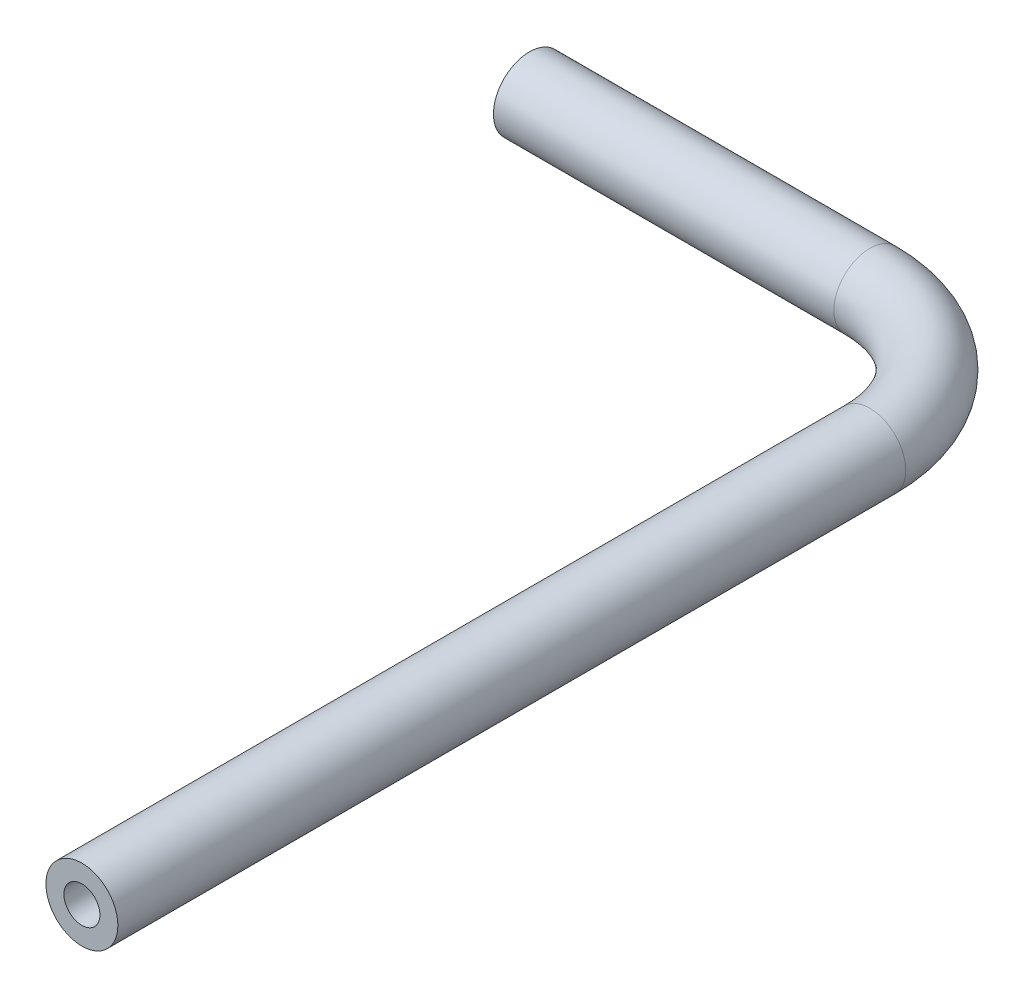
SolidWorks part; units mm, degrees
ref_plane "Front Plane" through (0, 0, 0) normal (0, 0, 1) x (1, 0, 0)
ref_plane "Top Plane" through (0, 0, 0) normal (0, 1, 0) x (1, 0, 0)
ref_plane "Right Plane" through (0, 0, 0) normal (1, 0, 0) x (0, 0, -1)
sketch "Sketch10" plane through (0, 0, 0) normal (0, 1, 0) x (1, 0, 0)
  line L0 (60.8594, -106.5557) -> (60.8594, -6.4079)
  line L1 (43.2668, 11.1847) -> (0, 11.1847)
  line L2 (0, -55) -> (0, 55) construction
  arc A0 (60.8594, -6.4079) -> (43.2668, 11.1847) centre (43.2668, -6.4079) ccw
  point P4 (0, 0)
  point P9 (0, 11.1847)
sketch "Sketch11" plane through (0, 0, 0) normal (1, 0, 0) x (0, 0, -1)
  circle A0 centre (11.1847, 0) radius 4.572
  circle A1 centre (11.1847, 0) radius 2.286
  dimension "D1" = 9.144
  dimension "D2" = 4.572
sweep "Sweep4" add profiles "Sketch11" path "Sketch10"
